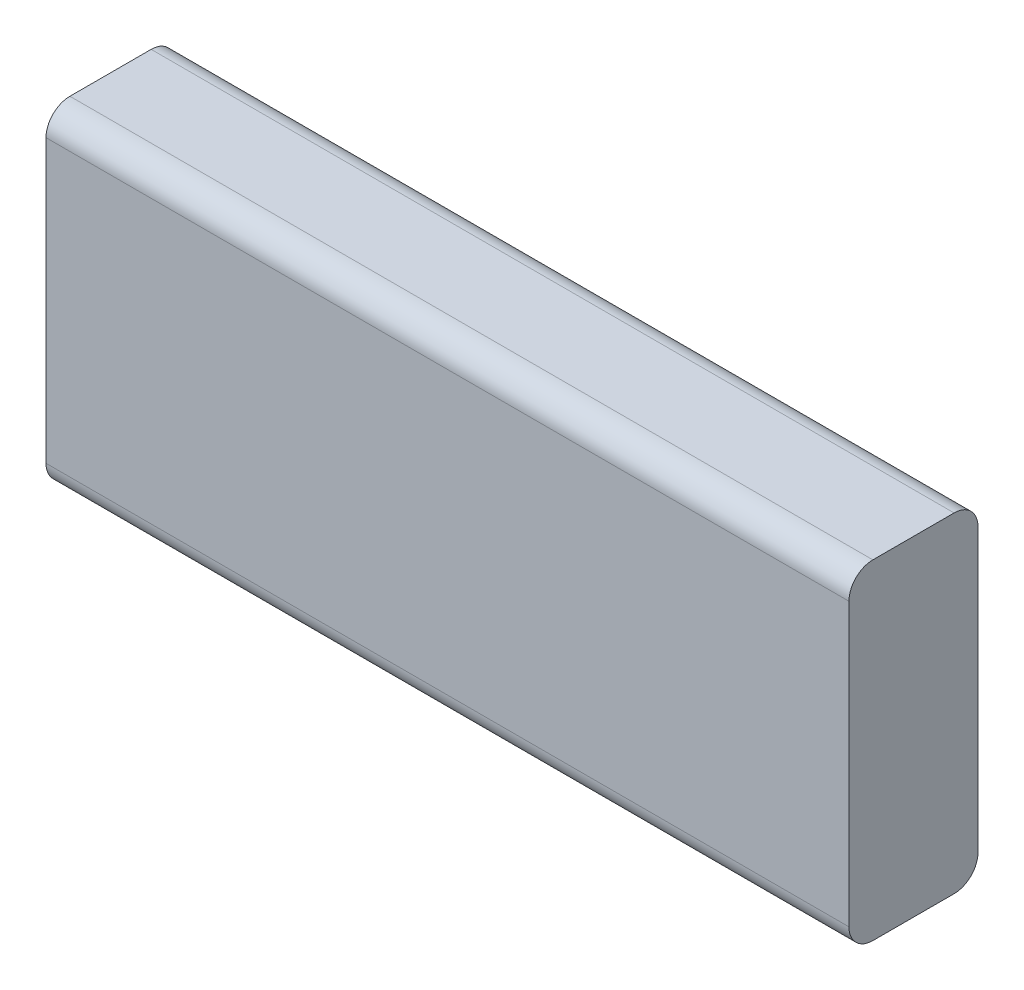
SolidWorks part; units mm, degrees
ref_plane "Plan de face" through (0, 0, 0) normal (0, 0, 1) x (1, 0, 0)
ref_plane "Plan de dessus" through (0, 0, 0) normal (0, 1, 0) x (1, 0, 0)
ref_plane "Plan de droite" through (0, 0, 0) normal (1, 0, 0) x (0, 0, -1)
sketch "Esquisse2" plane through (0, 0, 0) normal (0, 0, 1) x (1, 0, 0)
  line L1 (0, 0) -> (168, 0)
  line L2 (0, 0) -> (0, -69)
  line L3 (0, -69) -> (168, -69)
  line L4 (168, 0) -> (168, -69)
  dimension "D1" = 168
  dimension "D2" = 69
extrude "Boss.-Extru.1" add sketch "Esquisse2" along normal blind 27
fillet "Congé1" radius 5 4 edges at (84, -69, 27) (84, -69, 0) (84, 0, 0) (84, 0, 27)
sketch "Esquisse3" plane through (0, 0, 0) normal (0, 0, -1) x (-1, 0, 0)
  line L0 (-168, -34.5) -> (0, -34.5) construction
  line L1 (-168, -64) -> (-168, -5) construction
  line L2 (0, -5) -> (0, -64) construction
  text T0 "Batterie  Turnigy Graphene Panther 6000 mAh LiPo"
extrude "Enlèv. mat.-Extru.1" cut sketch "Esquisse3" against normal blind 5
